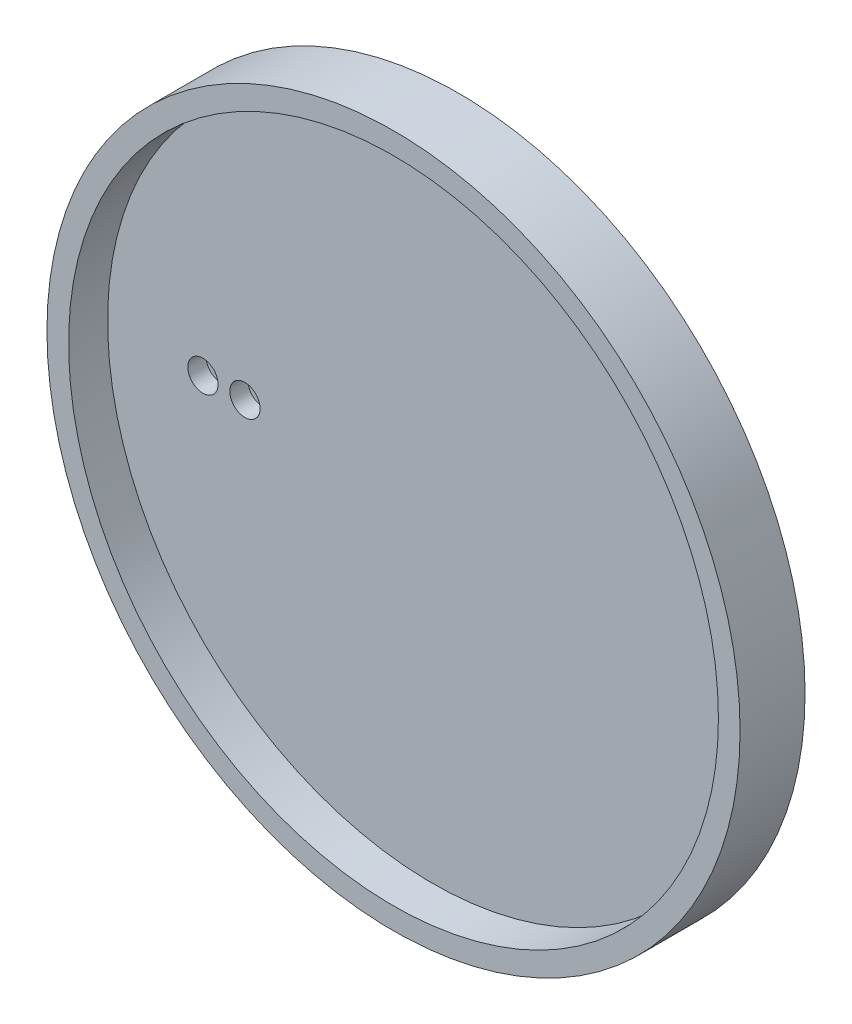
SolidWorks part; units mm, degrees
ref_plane "Front Plane" through (0, 0, 0) normal (0, 0, 1) x (1, 0, 0)
ref_plane "Top Plane" through (0, 0, 0) normal (0, 1, 0) x (1, 0, 0)
ref_plane "Right Plane" through (0, 0, 0) normal (1, 0, 0) x (0, 0, -1)
sketch "Sketch1" plane through (0, 0, 0) normal (0, 1, 0) x (1, 0, 0)
  line L0 (-58.5761, 0) -> (16.4239, 0)
  line L1 (16.4239, 0) -> (16.4239, 5)
  line L2 (16.4239, 5) -> (-37.7115, 5)
  line L3 (-37.7115, 5) -> (-37.7115, 10)
  line L4 (-58.5761, 0) -> (-58.5761, 10)
  line L5 (-58.5761, 10) -> (-37.7115, 10)
  dimension "D1" = 75
  dimension "D2" = 10
  dimension "D3" = 5
extrude "Boss-Extrude1" add sketch "Sketch1" along normal blind 12.7
sketch "Sketch2" plane through (0, 0, -10) normal (0, 0, -1) x (-1, 0, 0)
  line L0 (58.5761, 6.35) -> (37.7115, 6.35)
  line L1 (58.5761, 12.7) -> (58.5761, 0) construction
  line L2 (37.7115, 12.7) -> (37.7115, 0) construction
  line L3 (41.2438, 6.35) -> (41.2438, 0)
  line L4 (37.7115, 0) -> (58.5761, 0) construction
  line L5 (55.0438, 1.6197) -> (58.5761, 1.6197)
  line L6 (55.0438, 6.35) -> (55.0438, 0)
  line L7 (37.7115, 2.551) -> (41.2438, 2.551)
  line L8 (37.7115, 12.7) -> (37.7115, 0) construction
  circle A0 centre (43.2938, 6.35) radius 2.05
  circle A1 centre (52.9938, 6.35) radius 2.05
  dimension "D1" = 4.1
  dimension "D2" = 13.8
extrude "Cut-Extrude1" cut sketch "Sketch2" against normal blind 12.7 contours L0 A0 | L0 A0 | L0 A1 | L0 A1 region at (-43.2938, 5.48, -10) region at (-52.9938, 7.22, -10) region at (-52.9938, 5.48, -10) region at (-43.2938, 7.22, -10)
sketch "Sketch3" plane through (0, 0, 0) normal (0, 0, 1) x (1, 0, 0)
  line L0 (-41.2438, 6.35) -> (16.4239, 6.35)
  line L1 (16.4239, 12.7) -> (16.4239, 0) construction
  circle A0 centre (-43.2938, 6.35) radius 2.05 construction
  circle A1 centre (0, 6.35) radius 75
  circle A2 centre (0, 6.35) radius 80
  circle M1 centre (-43.2938, 6.35) radius 2.05
  circle M2 centre (-52.9938, 6.35) radius 2.05
  line M3 (-58.5761, 0) -> (16.4239, 0)
  line M4 (16.4239, 0) -> (16.4239, 12.7)
  line M5 (16.4239, 12.7) -> (-58.5761, 12.7)
  line M6 (-58.5761, 12.7) -> (-58.5761, 0)
  dimension "D1" = 150
  dimension "D2" = 5
extrude "Boss-Extrude2" add sketch "Sketch3" along normal blind 6 contours A1 M3 M6 M5 M4 | M1 M4 M5 M6 M3 M2 region at (15.6632, 3.175, 0) region at (-72.8787, 6.35, 0)
extrude "Boss-Extrude3" add sketch "Sketch3<4>" along normal blind 15 contours A2 A1 region at (-77.7373, 6.35, 0)
sketch "Sketch3<4>" plane through (0, 0, 0) normal (0, 0, 1) x (1, 0, 0) same geometry as "Sketch3"
sketch "Sketch4" plane through (0, 0, 6) normal (0, 0, 1) x (1, 0, 0)
  circle A0 centre (-52.9938, 6.35) radius 3.5
  circle A1 centre (-43.2938, 6.35) radius 3.5
  dimension "D1" = 7
  dimension "D2" = 7
extrude "Cut-Extrude2" cut sketch "Sketch4" against normal blind 4.2
